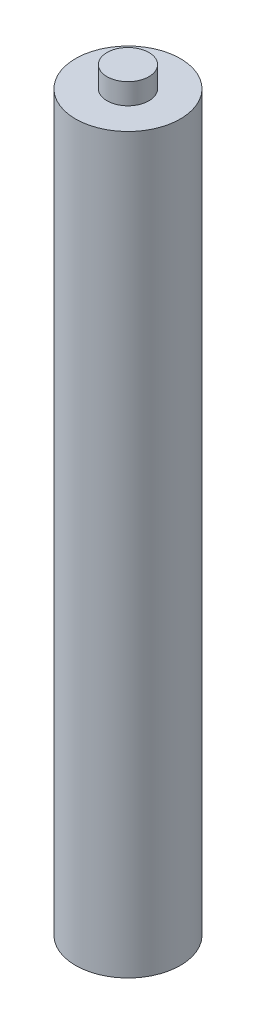
SolidWorks part; units mm, degrees
ref_plane "Front Plane" through (0, 0, 0) normal (0, 0, 1) x (1, 0, 0)
ref_plane "Top Plane" through (0, 0, 0) normal (0, 1, 0) x (1, 0, 0)
ref_plane "Right Plane" through (0, 0, 0) normal (1, 0, 0) x (0, 0, -1)
sketch "Sketch1" plane through (0, 0, 0) normal (0, 1, 0) x (1, 0, 0)
  circle A0 centre (0, 0) radius 12.7
  dimension "D1" = 25.4
extrude "Boss-Extrude1" add sketch "Sketch1" along normal blind 177.8
sketch "Sketch4" plane through (0, 177.8, 0) normal (0, 1, 0) x (1, 0, 0)
  circle A2 centre (0, 0) radius 5.08
  circle A3 centre (0, 0) radius 5.08
  dimension "D1" = 7.62
extrude "Boss-Extrude2" add sketch "Sketch4" along normal blind 5.08
